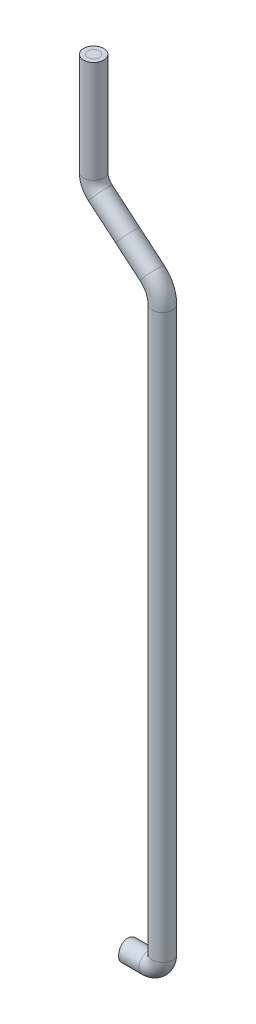
SolidWorks part; units mm, degrees
material "Изоляция провода красная"
ref_plane "Спереди" through (0, 0, 0) normal (0, 0, 1) x (1, 0, 0)
ref_plane "Сверху" through (0, 0, 0) normal (0, 1, 0) x (1, 0, 0)
ref_plane "Справа" through (0, 0, 0) normal (1, 0, 0) x (0, 0, -1)
sketch "Эскиз1" plane through (0, 0, 0) normal (0, 1, 0) x (1, 0, 0)
  circle A0 centre (0, 0) radius 1.05
  dimension "D1" = 2.1
sketch "Эскиз2" plane through (0, 0, 0) normal (0, 0, 1) x (1, 0, 0)
  line L0 (0, 0) -> (0, 50000) construction
  line L1 (0, 0) -> (0, 58.4803)
  line L2 (-3.6, 40.1771) -> (-3.6, 50040.1771) construction
  line L3 (-1.0716, 60.7785) -> (-3.6, 62.9)
  line L4 (-3.6, 62.9) -> (-6.4356, 65.2793)
  line L5 (-6.1, 56.0945) -> (-6.1, -49943.9055) construction
  line L6 (-7.15, 66.8114) -> (-7.15, 77.4195)
  arc A0 (0, 58.4803) -> (-1.0716, 60.7785) centre (-3, 58.4803) ccw
  arc A1 (-6.4356, 65.2793) -> (-7.15, 66.8114) centre (-5.15, 66.8114) cw
  point P10 (0, 59.8792)
  point P17 (-7.15, 65.8788)
  dimension "D4" = 3
  dimension "D8" = 2
  dimension "D1" = 59.8792
  dimension "D2" = 3.6
  dimension "D3" = 50
  dimension "D5" = 1.05
  dimension "D6" = 2.5
  dimension "D7" = 10.6081
sweep "По траектории1" add profiles "Эскиз1" path "Эскиз2"
sketch "Эскиз3" plane through (0, 0, 0) normal (0, -1, 0) x (1, 0, 0)
  circle A0 centre (0, 0) radius 0.6
  dimension "D1" = 1.2
sweep "Вырез-По траектории1" cut profiles "Эскиз3" path "Эскиз2<2>"
sketch "Эскиз2<2>" plane through (0, 0, 0) normal (0, 0, 1) x (1, 0, 0) same geometry as "Эскиз2"
sketch "Эскиз4" plane through (0, 0, 0) normal (0, -1, 0) x (1, 0, 0)
  circle A0 centre (0, 0) radius 0.6 construction
  circle A1 centre (0, 0) radius 0.6
sweep "По траектории2" add profiles "Эскиз4" path "Эскиз2<3>"
sketch "Эскиз2<3>" plane through (0, 0, 0) normal (0, 0, 1) x (1, 0, 0) same geometry as "Эскиз2"
sketch "Эскиз5" plane through (0, 0, 0) normal (0, -1, 0) x (1, 0, 0)
  circle A1 centre (0, 0) radius 0.6
  circle A2 centre (0, 0) radius 0.6
  dimension "D1" = 0
sketch "Эскиз6" plane through (0, 0, 0) normal (0, 0, 1) x (1, 0, 0)
  line L0 (0, 0) -> (0, -50000) construction
  line L1 (0, -1.4) -> (-50000, -1.4) construction
  line L2 (-1.05, 0) -> (1.05, 0) construction
  line L3 (-1.4, -1.4) -> (-3.6, -1.4)
  line L4 (-3.6, -1.4) -> (-3.6, 49998.6) construction
  line L5 (2.4, -1.4) -> (2.4, -50001.4) construction
  arc A0 (0, 0) -> (-1.4, -1.4) centre (-1.4, 0) cw
  dimension "D1" = 1.4
  dimension "D3" = 2.4
  dimension "D4" = 6
sweep "По траектории3" add profiles "Эскиз5" path "Эскиз6"
sketch "Эскиз7" plane through (0, 0, 0) normal (0, -1, 0) x (1, 0, 0)
  circle A0 centre (0, 0) radius 0.6 construction
  circle A1 centre (0, 0) radius 1.05
  circle A2 centre (0, 0) radius 1.05
  circle A3 centre (0, 0) radius 0.6
  dimension "D1" = 0
sweep "По траектории4" add profiles "Эскиз7" path "Эскиз6<2>"
sketch "Эскиз6<2>" plane through (0, 0, 0) normal (0, 0, 1) x (1, 0, 0) same geometry as "Эскиз6"
ref_plane "Плоскость1" through (0, -2.45, 0) normal (0, -1, 0) x (-1, 0, 0)
sketch "Эскиз8" plane through (0, -2.45, 0) normal (0, -1, 0) x (-1, 0, 0)
  line L0 (0, 0) -> (50000, 0) construction
  line L1 (3.6, -1.05) -> (3.6, 1.05) construction
  line L2 (3.6, -1.05) -> (3.6, 1.05)
  line L3 (3.6, 1.05) -> (3.5074, 1.05)
  line L5 (3.6, -1.05) -> (3.5074, -1.05)
  arc A0 (3.5074, -1.05) -> (3.5074, 1.05) centre (-2.4, 0) ccw
  dimension "D1" = 12
extrude "Вырез-Вытянуть2" cut sketch "Эскиз8" against normal blind 3 contours A0 L2 L3 region at (-3.5723, -2.45, -0.7879)
extrude "Вырез-Вытянуть3" cut sketch "Эскиз8<3>" against normal blind 3 contours A0 L5 L2 region at (-3.5723, -2.45, 0.7879)
sketch "Эскиз8<3>" plane through (0, -2.45, 0) normal (0, -1, 0) x (-1, 0, 0) same geometry as "Эскиз8"
